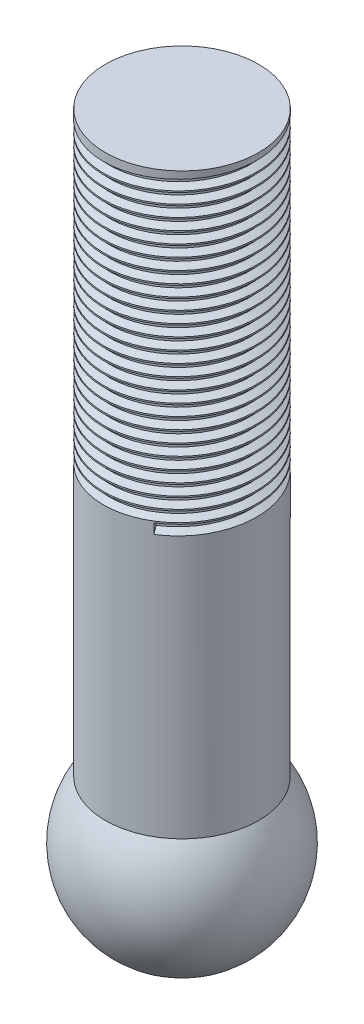
SolidWorks part; units mm, degrees
ref_plane "Front Plane" through (0, 0, 0) normal (0, 0, 1) x (1, 0, 0)
ref_plane "Top Plane" through (0, 0, 0) normal (0, 1, 0) x (1, 0, 0)
ref_plane "Right Plane" through (0, 0, 0) normal (1, 0, 0) x (0, 0, -1)
sketch "Sketch1" plane through (0, 0, 0) normal (0, 0, 1) x (1, 0, 0)
  line L0 (0, -12.5) -> (0, 12.5) construction
  line L1 (0, 12.5) -> (0, -12.5)
  arc A0 (0, -12.5) -> (0, 12.5) centre (0, 0) ccw
  point P4 (0, 0)
  dimension "D1" = 25
revolve "Revolve1" add sketch "Sketch1" angle 360 about L0
sketch "Sketch2" plane through (0, 0, 0) normal (0, 1, 0) x (1, 0, 0)
  circle A0 centre (0, 0) radius 10
  dimension "D1" = 20
extrude "Boss-Extrude1" add sketch "Sketch2" along normal blind 83
thread "Thread1" pitch 1.5 method cut profile "Thread Profile1" start angle 0, offset 0, length 40, pitch 1.5, diameter 20
ref_plane "Plane1" through (-10, 83, 0) normal (0, 0, 1) x (-1, 0, 0)
sketch "Thread Profile1" plane through (-10, 83, 0) normal (0, 0, 1) x (-1, 0, 0)
  line L0 (0, 0) -> (0, 1.5) construction
  line L11 (0, 0) -> (0, 1.3125)
  line L12 (0, 1.3125) -> (-0.8119, 0.8437)
  line L13 (-0.8119, 0.8437) -> (-0.8119, 0.4687)
  line L15 (-0.8119, 0.4687) -> (0, 0)
  line L17 (-0.8119, 0.6562) -> (0, 0.6562) construction
  point P2 (0, 0)
  dimension "Pitch" = 1.5
  dimension "Profile_Angle" = 60
  dimension "Profile_Land" = 0.375
  dimension "Profile_Height" = 0.8119
